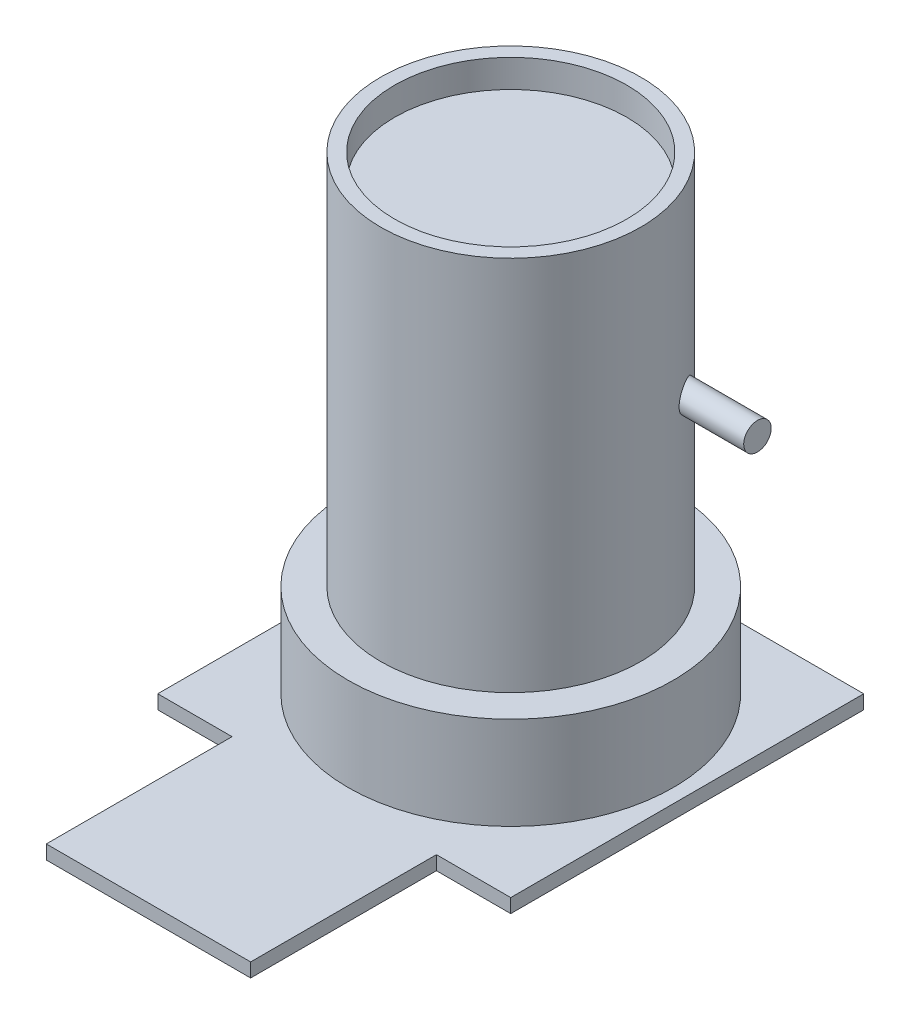
SolidWorks part; units mm, degrees
ref_plane "Front Plane" through (0, 0, 0) normal (0, 0, 1) x (1, 0, 0)
ref_plane "Top Plane" through (0, 0, 0) normal (0, 1, 0) x (1, 0, 0)
ref_plane "Right Plane" through (0, 0, 0) normal (1, 0, 0) x (0, 0, -1)
sketch "Sketch1" plane through (0, 0, 0) normal (0, 1, 0) x (1, 0, 0)
  line L1 (-19, 19) -> (19, 19)
  line L2 (-19, 19) -> (-19, -19)
  line L3 (-19, -19) -> (19, -19)
  line L4 (19, 19) -> (19, -19)
  point P4 (0, 19)
  point P6 (19, 0)
  dimension "D1" = 38
  dimension "D2" = 38
extrude "Boss-Extrude1" add sketch "Sketch1" along normal blind 1.5
sketch "Sketch2" plane through (0, 1.5, 0) normal (0, 1, 0) x (1, 0, 0)
  circle A0 centre (0, 0) radius 17.5
  point P2 (0, 0)
extrude "Boss-Extrude2" add sketch "Sketch2" along normal blind 10
sketch "Sketch3" plane through (0, 11.5, 0) normal (0, 1, 0) x (1, 0, 0)
  circle A0 centre (0, 0) radius 14
extrude "Boss-Extrude3" add sketch "Sketch3" along normal blind 40.5
sketch "Sketch4" plane through (0, 52, 0) normal (0, 1, 0) x (1, 0, 0)
  circle A0 centre (0, 0) radius 12.5
extrude "Cut-Extrude1" cut sketch "Sketch4" against normal blind 3
sketch "Sketch5" plane through (0, 0, 0) normal (1, 0, 0) x (0, 0, -1)
  line L0 (12.5, 52) -> (-12.5, 52) construction
  circle A0 centre (6.5586, 32.23) radius 1.4786
  dimension "D1" = 19.77
extrude "Boss-Extrude4" add sketch "Sketch5" along normal blind 20
sketch "Sketch6" plane through (0, 0, 19) normal (0, 0, 1) x (1, 0, 0)
  line L0 (-11, 1.5) -> (-11, 0)
  line L1 (-19, 1.5) -> (19, 1.5) construction
  line L2 (-19, 0) -> (19, 0) construction
  line L3 (-11, 0) -> (11, 0)
  line L4 (11, 0) -> (11, 1.5)
  line L5 (11, 1.5) -> (-11, 1.5)
  line L7 (-19, 1.5) -> (-19, 0) construction
  point P7 (0, 1.5)
  dimension "D1" = 22
  dimension "D2" = 19
extrude "Boss-Extrude5" add sketch "Sketch6" along normal blind 20
